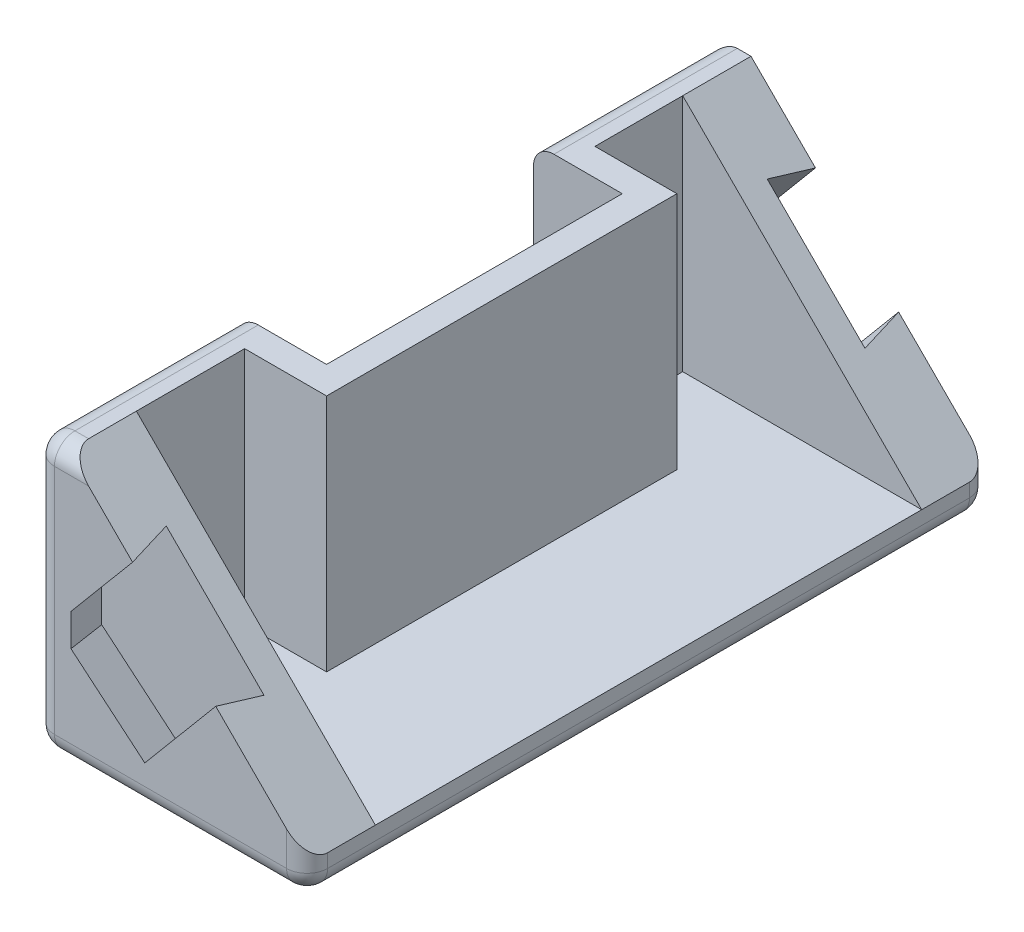
SolidWorks part; units mm, degrees
ref_plane "前视基准面" through (0, 0, 0) normal (0, 0, 1) x (1, 0, 0)
ref_plane "上视基准面" through (0, 0, 0) normal (0, 1, 0) x (1, 0, 0)
ref_plane "右视基准面" through (0, 0, 0) normal (1, 0, 0) x (0, 0, -1)
sketch "草图1" plane through (0, 0, 0) normal (0, 0, 1) x (1, 0, 0)
  line L0 (0, 0) -> (-100, -119.1754)
  line L1 (-100, -119.1754) -> (-55, -119.1754)
  line L2 (100, -119.1754) -> (0, 0)
  line L3 (-100, -119.1754) -> (-100, -74.1754)
  line L4 (-100, -74.1754) -> (-55, -119.1754)
  line L6 (0, 0) -> (0, 50000) construction
  line L7 (0, 15.5572) -> (-96, -98.8511)
  line L8 (-10.5203, -28.0949) -> (-83.5895, -115.1754)
  line L9 (7.6604, -6.4279) -> (-92.3396, -125.6032) construction
  line L10 (-7.6604, 6.4279) -> (-107.6604, -112.7475) construction
  line L13 (0, 0) -> (-42.5357, 0) construction
  line L14 (0, -119.1754) -> (100, -119.1754)
  line L21 (-96, -104.7617) -> (-83.5895, -115.1754)
  line L22 (-96, -119.1754) -> (-96, -88.5856) construction
  line L23 (-96, -98.8511) -> (-96, -104.7617)
  line L24 (1.1491, 14.5931) -> (-94.5, -99.3971)
  line L25 (-94.5, -99.3971) -> (-94.5, -104.0623)
  line L26 (-94.5, -104.0623) -> (-83.7744, -113.0621)
  line L27 (-11.6694, -27.1307) -> (-83.7744, -113.0621)
  line L28 (-81.6478, -81.7469) -> (-66.327, -94.6026)
  circle A0 centre (0, 0) radius 4
  circle A1 centre (0, 0) radius 11.15
  circle A2 centre (0, 0) radius 30
  dimension "D4" = 8
  dimension "D11" = 22.3
  dimension "D12" = 60
  dimension "D1" = 200
  dimension "D2" = 50
  dimension "D3" = 45
  dimension "D7" = 45
  dimension "D8" = 4
  dimension "D9" = 4
  dimension "D10" = 1.5
  dimension "D5" = 10
  dimension "D6" = 10
sketch "草图3" plane through (0, 0, 0) normal (0, 0, 1) x (1, 0, 0)
  line L0 (-100, -119.1754) -> (-55, -119.1754) construction
  line L1 (-100, -74.1754) -> (-55, -119.1754) construction
  line L2 (-100, -119.1754) -> (-100, -74.1754) construction
  line L3 (-100, -119.1754) -> (-55, -119.1754)
  line L4 (-100, -74.1754) -> (-55, -119.1754)
  line L5 (-100, -119.1754) -> (-100, -74.1754)
  line L6 (-100, -79.1754) -> (-95, -79.1754)
  line L7 (-60, -114.1754) -> (-60, -119.1754)
  dimension "D1" = 5
  dimension "D2" = 5
extrude "凸台-拉伸1" add sketch "草图3" against normal blind 10 contours L7 L4 L6 L5 L3
sketch "草图8" plane through (0, 0, 0) normal (0, 0, 1) x (1, 0, 0)
  line L46 (-81.6478, -81.7469) -> (-66.327, -94.6026) construction
  line L47 (-80.5601, -82.6596) -> (-67.4147, -93.6899)
  line L50 (-94.58, -99.3679) -> (1.0878, 14.6445)
  line L56 (-11.6081, -27.1821) -> (-83.7646, -113.1748)
  line L57 (-83.7646, -113.1748) -> (-94.58, -104.0996)
  line L58 (-94.58, -104.0996) -> (-94.58, -99.3679)
  line L59 (-94.58, -99.3679) -> (-80.5601, -82.6596)
  line L60 (-67.4147, -93.6899) -> (-83.7646, -113.1748)
  line L61 (-83.7646, -113.1748) -> (-94.58, -104.0996)
  line L62 (-94.58, -104.0996) -> (-94.58, -99.3679)
  dimension "D1" = 0.08
ref_plane "基准面1" through (0, 0, -6) normal (0, 0, 1) x (1, 0, 0)
sketch "草图5" plane through (0, 0, -6) normal (0, 0, 1) x (1, 0, 0)
  line L19 (-1.5366, 10.948) -> (0.8296, 14.9915)
  line L41 (-1.9367, 19.372) -> (0.4289, -30.4396)
  line L42 (-1.5366, 10.948) -> (0.8296, 14.9915)
  line L69 (-81.6478, -81.7469) -> (-66.327, -94.6026) construction
  line L70 (-81.7091, -81.6955) -> (-66.2657, -94.6541)
  line L71 (-1.6671, 13.6949) -> (-0.0613, 15.6087)
  line L73 (-96.08, -98.822) -> (-0.0613, 15.6087)
  line L74 (-10.4591, -28.1463) -> (-83.5797, -115.2881)
  line L75 (-83.5797, -115.2881) -> (-96.08, -104.799)
  line L76 (-96.08, -104.799) -> (-96.08, -98.822)
  line L77 (-96.08, -98.822) -> (-81.7091, -81.6955)
  line L78 (-66.2657, -94.6541) -> (-83.5797, -115.2881)
  line L79 (-83.5797, -115.2881) -> (-96.08, -104.799)
  line L80 (-96.08, -104.799) -> (-96.08, -98.822)
  dimension "D1" = 0.08
loft "切除-放样1" cut section "草图5" section "草图8" connector at (-96.08, -98.822, -6) connector at (-94.58, -99.3679, 0)
sketch "草图9" plane through (0, 0, -10) normal (0, 0, -1) x (-1, 0, 0)
  line L0 (100, -119.1754) -> (55, -119.1754) construction
  line L1 (100, -119.1754) -> (100, -74.1754) construction
  line L2 (100, -119.1754) -> (60, -119.1754)
  line L3 (100, -119.1754) -> (100, -79.1754)
  line L4 (95, -79.1754) -> (95, -114.1754)
  line L5 (60, -114.1754) -> (60, -119.1754)
  line L6 (60, -119.1754) -> (100, -119.1754)
  line L7 (100, -119.1754) -> (100, -79.1754)
  line L8 (100, -79.1754) -> (95, -79.1754)
  line L9 (95, -79.1754) -> (60, -114.1754)
  line L10 (60, -114.1754) -> (60, -119.1754)
  line L11 (60, -119.1754) -> (100, -119.1754)
  line L12 (100, -119.1754) -> (100, -79.1754)
  line L13 (100, -79.1754) -> (95, -79.1754)
  line L15 (95, -114.1754) -> (60, -114.1754)
  line M7 (60, -114.1754) -> (60, -119.1754)
  line M8 (60, -119.1754) -> (100, -119.1754)
  line M9 (100, -119.1754) -> (100, -79.1754)
  line M10 (100, -79.1754) -> (95, -79.1754)
  dimension "D1" = 0
extrude "凸台-拉伸3" add sketch "草图9" along normal blind 40 contours L4 L15 M7 M8 M9 M10
mirror "镜向2" about plane through (0, 0, -50) normal (0, 0, -1) of bodies 112
fillet "圆角2" radius 3 6 edges at (-60, -116.6754, -100) (-60, -116.6754, 0) (-100, -99.1754, -100) (-100, -99.1754, 0) (-100, -79.1754, -50) (-97.5, -79.1754, 0)
fillet "圆角3" radius 3 8 edges at (-99.1213, -119.1754, -0.8787) (-100, -119.1754, -50) (-99.1213, -119.1754, -99.1213) (-80, -119.1754, -100) (-60.8787, -119.1754, -99.1213) (-60, -119.1754, -50) (-60.8787, -119.1754, -0.8787) (-80, -119.1754, 0)
sketch "草图10" plane through (-100, 0, 0) normal (-1, 0, 0) x (0, 0, 1)
  line L0 (-51.5, -79.1754) -> (-51.5, -119.1754) construction
  line L1 (-100, -79.1754) -> (-3, -79.1754) construction
  line L2 (-3, -119.1754) -> (-97, -119.1754) construction
  line L3 (-90, -114.1754) -> (-10, -114.1754) construction
  line L5 (-29.85, -114.1754) -> (-29.85, -79.1754)
  line L7 (-73.15, -114.1754) -> (-73.15, -79.1754)
  line L8 (-51.5, -79.1754) -> (-51.5, -119.1754) construction
  line L9 (-29.85, -96.6754) -> (-73.15, -96.6754) construction
  line L10 (-73.15, -114.1754) -> (-29.85, -114.1754)
  line L11 (-73.15, -79.1754) -> (-29.85, -79.1754)
  point P6 (-51.5, -96.6754)
  dimension "D2" = 43.3
extrude "切除-拉伸1" cut sketch "草图10" against normal blind 12.8
sketch "草图11" plane through (0, -114.1754, 0) normal (0, 1, 0) x (1, 0, 0)
  line L0 (-83, 25.85) -> (-95, 25.85)
  line L1 (-60, 50) -> (-50060, 50) construction
  line L2 (-60, 90) -> (-60, 10) construction
  line L4 (-83, 77.15) -> (-83, 25.85)
  line L9 (-95, 29.85) -> (-95, 10) construction
  line L13 (-83, 77.15) -> (-95, 77.15)
  line L14 (-95, 90) -> (-95, 73.15) construction
  line L15 (-95, 77.15) -> (-95, 73.15)
  line L16 (-95, 29.85) -> (-95, 25.85)
  line L18 (-95, 73.15) -> (-87, 73.15)
  line L19 (-87, 73.15) -> (-87, 29.85)
  line L20 (-87, 29.85) -> (-95, 29.85)
  line L21 (-100, 73.15) -> (-100, 29.85) construction
  point P4 (-60, 50)
  dimension "D1" = 4
  dimension "D2" = 13
  dimension "D3" = 4
  dimension "D4" = 4
extrude "凸台-拉伸4" add sketch "草图11" along normal up to surface (35 mm away) up to face at (-95.8, -79.1754, -87.26)
sketch "草图12" plane through (0, -79.1754, 0) normal (0, 1, 0) x (1, 0, 0)
  line L0 (-95, 77.15) -> (-83, 77.15) construction
  line L1 (-83, 25.85) -> (-100, 25.85)
  line L2 (-83, 25.85) -> (-83, 77.15)
  line L3 (-83, 77.15) -> (-100, 77.15)
  line L4 (-100, 25.85) -> (-100, 77.15)
  line L5 (-91.5, 77.15) -> (-91.5, 25.85) construction
  line L6 (-83, 51.5) -> (-100, 51.5) construction
  line L7 (-95, 25.85) -> (-83, 25.85) construction
  line L8 (-83, 77.15) -> (-83, 25.85) construction
  line L9 (-100, 73.15) -> (-100, 29.85) construction
  line L11 (-49.5567, -0.9458) -> (-111.1305, -0.9458)
  line L12 (-49.5567, -0.9458) -> (-49.5567, 103.9458)
  line L13 (-49.5567, 103.9458) -> (-111.1305, 103.9458)
  line L14 (-111.1305, -0.9458) -> (-111.1305, 103.9458)
  line L15 (-80.3436, 103.9458) -> (-80.3436, -0.9458) construction
  line L16 (-49.5567, 51.5) -> (-111.1305, 51.5) construction
  point P0 (-91.5, 51.5)
  point P15 (-80.3436, 51.5)
extrude "切除-拉伸2" [suppressed] cut sketch "草图12" against normal through all
ref_plane "基准面2" through (0, 0, -10) normal (0, 0, -1) x (-1, 0, 0)
other "使用曲面切除1"
